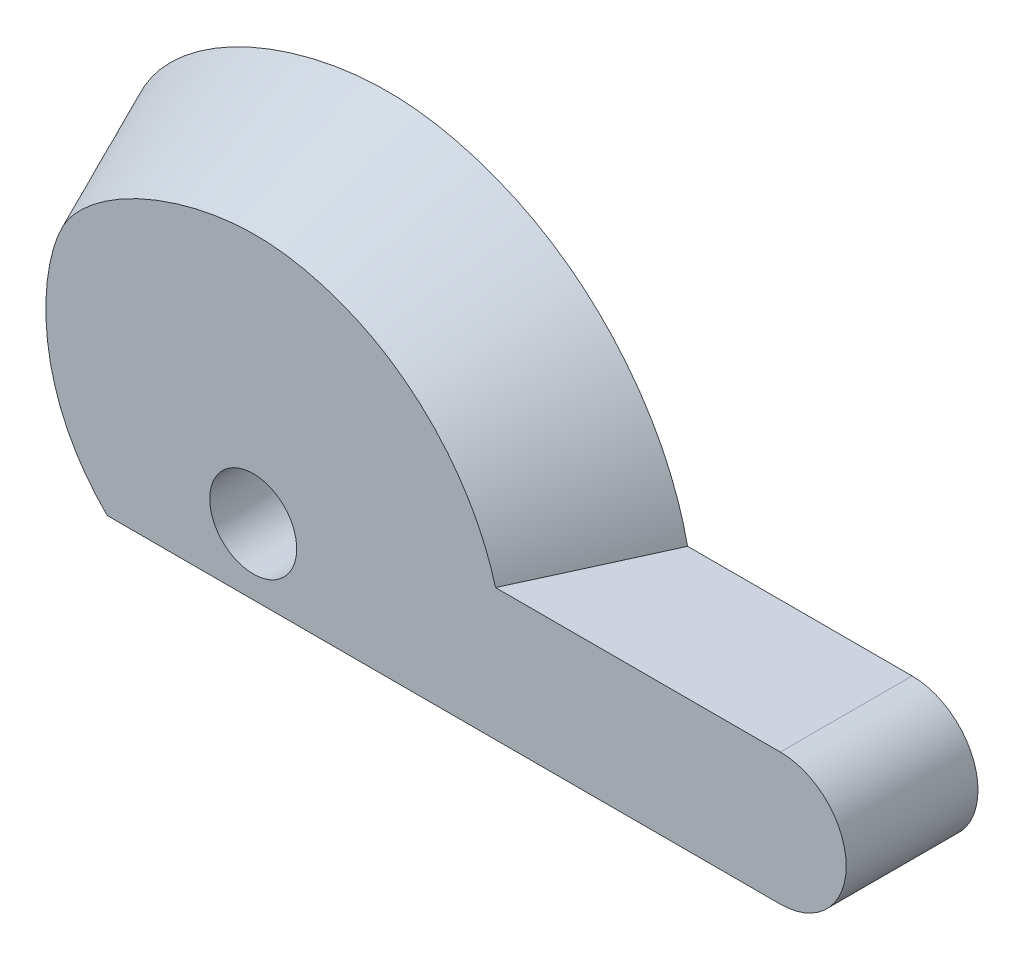
SolidWorks part; units mm, degrees
ref_plane "Plano frontal" through (0, 0, 0) normal (0, 0, 1) x (1, 0, 0)
ref_plane "Plano superior" through (0, 0, 0) normal (0, 1, 0) x (1, 0, 0)
ref_plane "Plano direito" through (0, 0, 0) normal (1, 0, 0) x (0, 0, -1)
sketch "Esboço2" plane through (0, 0, 0) normal (0, 0, 1) x (1, 0, 0)
  line L0 (20, 2.5) -> (11.481, 2.5)
  line L1 (20, -2.5) -> (7.0711, -2.5)
  line L2 (0, 0) -> (-4.0151, -6.3348) construction
  line L3 (0, 0) -> (-5.7095, 4.8633) construction
  line L5 (-3.5951, 3.0623) -> (-8.9449, 7.6192) construction
  arc A0 (20, -2.5) -> (20, 2.5) centre (20, 0) ccw
  circle A1 centre (0, 0) radius 1.65
  circle A2 centre (0, 0) radius 7.5 construction
  circle A3 centre (0, 0) radius 11.75 construction
  spline S0 degree 3 poles (7.0711, -2.5) (5.2161, -5.6764) (2.5521, -8.0818) (-2.9441, -7.0146) (-3.695, -6.5168) (-10.7771, -2.3678) (-10.5296, 5.3737) (-7.3393, 9.9902) (-2.0083, 12.1047) (2.8435, 11.5834) (7.8737, 9.4913) (10.7845, 5.7687) (11.481, 2.5) knots 0 0 0 0 0.07466 0.136902 0.157574 0.182845 0.366634 0.411246 0.605993 0.705625 0.789136 1 1 1 1
  point P12 (0, 0)
  point P14 (-9.0508, 8.6217)
  point P16 (-2.0591, -4.5563)
  point P17 (-3.2176, -3.8272)
  point P20 (-3.6546, -6.5493)
  point P23 (-10.5579, 6.6918)
  point P25 (-8.6301, 9.0428)
  point P27 (-0.9409, 12.4645)
  point P29 (11.0313, 5.8788)
  point P30 (-7.2918, 10.1528)
  point P33 (-9.5158, 8.1055)
  dimension "D1" = 3.3
  dimension "D2" = 15
  dimension "D3" = 23.5
  dimension "D4" = 2.5
  dimension "D5" = 20
extrude "Ressalto-extrusão1" add sketch "Esboço2" along normal blind 5
chamfer "Chanfro1" distance 5 angle 24 1 edges
sketch "Esboço3" plane through (0, 0, 5) normal (0, 0, 1) x (1, 0, 0)
  line L0 (4.4553, -2.5) -> (20, -2.5) construction
  line L1 (7.7033, -2.5) -> (-22.7273, -2.5)
  line L2 (7.7033, -2.5) -> (7.7033, -13.5752)
  line L3 (7.7033, -13.5752) -> (-22.7273, -13.5752)
  line L4 (-22.7273, -2.5) -> (-22.7273, -13.5752)
  point P6 (-7.7556, -9.957)
  point P7 (-7.7556, -2.5)
  point P8 (-22.7273, -13.5752)
extrude "Corte-extrusão1" cut sketch "Esboço3" against normal blind 5
mirror "Espelhar3" about plane through (0, 0, 0) normal (0, 0, 1) of bodies 102
sketch "Esboço4" plane through (0, 0, 0) normal (0, 0, 1) x (1, 0, 0)
  line L1 (-59.921, -16.1439) -> (59.921, -16.1439)
  line L2 (-59.921, -16.1439) -> (-59.921, 16.1439)
  line L3 (-59.921, 16.1439) -> (59.921, 16.1439)
  line L4 (59.921, -16.1439) -> (59.921, 16.1439)
  line L5 (-59.921, -16.1439) -> (59.921, 16.1439) construction
  line L6 (-59.921, 16.1439) -> (59.921, -16.1439) construction
  point P0 (0, 0)
extrude "Corte-extrusão2" cut sketch "Esboço4" along normal blind 10
